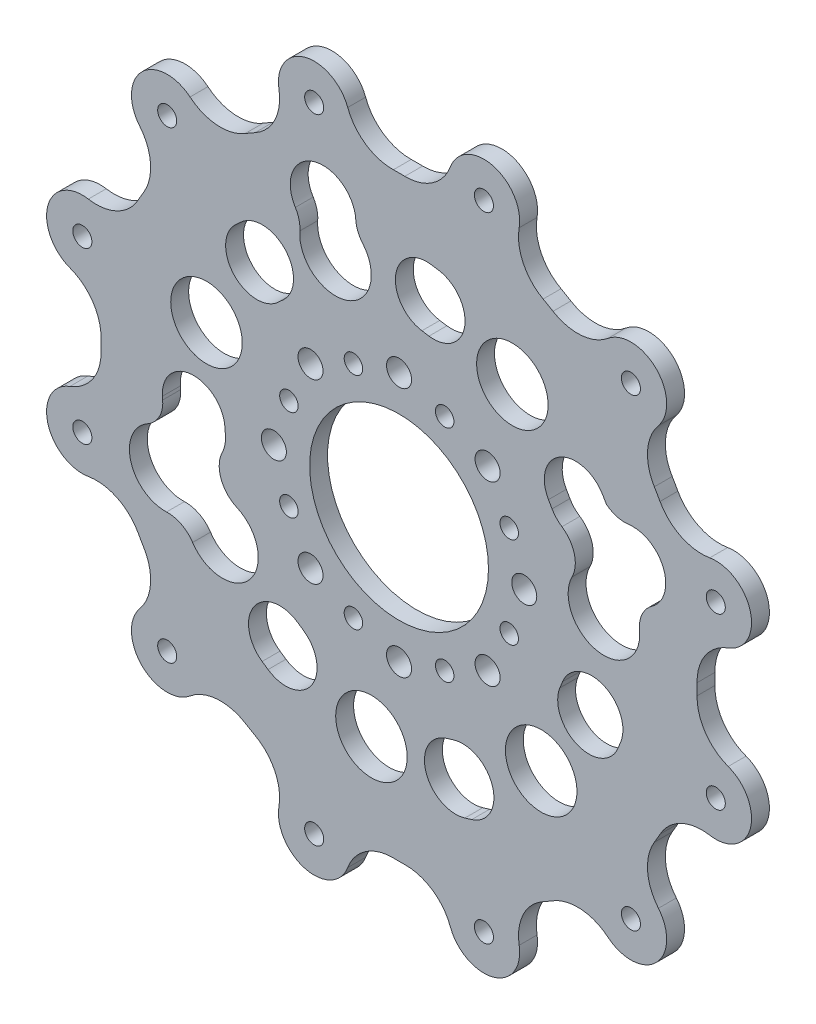
SolidWorks part; units mm, degrees
ref_plane "Front Plane" through (0, 0, 0) normal (0, 0, 1) x (1, 0, 0)
ref_plane "Top Plane" through (0, 0, 0) normal (0, 1, 0) x (1, 0, 0)
ref_plane "Right Plane" through (0, 0, 0) normal (1, 0, 0) x (0, 0, -1)
sketch "Sketch1" plane through (0, 0, 0) normal (0, 0, 1) x (1, 0, 0)
  line L0 (-65, 0) -> (-65, -65) construction
  line L2 (65, -65) -> (65, 0) construction
  line L7 (-65, -65) -> (65, -65) construction
  circle A0 centre (0, 0) radius 15
  arc A1 (65, 0) -> (-65, 0) centre (0, 0) ccw
  arc A2 (-65, 0) -> (0, -65) centre (0, 0) ccw
  arc A3 (0, -65) -> (65, 0) centre (0, 0) ccw
  dimension "D1" = 130
  dimension "D2" = 30
extrude "Boss-Extrude1" add sketch "Sketch1" along normal blind 3
sketch "Sketch2" plane through (0, 0, 3) normal (0, 0, 1) x (1, 0, 0)
  line L0 (0, 0) -> (0, 61) construction
  circle A0 centre (0, 61) radius 2.5
  circle A1 centre (52.8275, 30.5) radius 2.5
  circle A2 centre (52.8275, -30.5) radius 2.5
  circle A3 centre (0, -61) radius 2.5
  circle A4 centre (-52.8275, -30.5) radius 2.5
  circle A5 centre (-52.8275, 30.5) radius 2.5
  point P16 (0, 0)
  dimension "D1" = 5
  dimension "D2" = 61
  dimension "D3" = 6
extrude "Cut-Extrude1" cut sketch "Sketch2" against normal through all
sketch "Sketch3" plane through (0, 0, 3) normal (0, 0, 1) x (1, 0, 0)
  line L0 (0, 0) -> (14.235, 53.1259) construction
  line L1 (0, 0) -> (0, 26.2737) construction
  circle A0 centre (14.235, 53.1259) radius 1.6
  circle A1 centre (38.8909, 38.8909) radius 1.6
  circle A2 centre (53.1259, 14.235) radius 1.6
  circle A3 centre (53.1259, -14.235) radius 1.6
  circle A4 centre (38.8909, -38.8909) radius 1.6
  circle A5 centre (14.235, -53.1259) radius 1.6
  circle A6 centre (-14.235, -53.1259) radius 1.6
  circle A7 centre (-38.8909, -38.8909) radius 1.6
  circle A8 centre (-53.1259, -14.235) radius 1.6
  circle A9 centre (-53.1259, 14.235) radius 1.6
  circle A10 centre (-38.8909, 38.8909) radius 1.6
  circle A11 centre (-14.235, 53.1259) radius 1.6
  point P29 (0, 0)
  dimension "D1" = 3.2
  dimension "D2" = 55
  dimension "D3" = 15
  dimension "D4" = 12
extrude "Cut-Extrude2" cut sketch "Sketch3" against normal through all
sketch "Sketch4" plane through (0, 0, 3) normal (0, 0, 1) x (1, 0, 0)
  line L0 (0, 21) -> (0, 0) construction
  line L1 (0, 0) -> (7.6537, 18.4776) construction
  circle A0 centre (0, 21) radius 2.1
  circle A1 centre (7.6537, 18.4776) radius 1.55
  circle A2 centre (14.8492, 14.8492) radius 2.1
  circle A3 centre (18.4776, 7.6537) radius 1.55
  circle A4 centre (21, 0) radius 2.1
  circle A5 centre (18.4776, -7.6537) radius 1.55
  circle A6 centre (14.8492, -14.8492) radius 2.1
  circle A7 centre (7.6537, -18.4776) radius 1.55
  circle A8 centre (0, -21) radius 2.1
  circle A9 centre (-7.6537, -18.4776) radius 1.55
  circle A10 centre (-14.8492, -14.8492) radius 2.1
  circle A11 centre (-18.4776, -7.6537) radius 1.55
  circle A12 centre (-21, 0) radius 2.1
  circle A13 centre (-18.4776, 7.6537) radius 1.55
  circle A14 centre (-14.8492, 14.8492) radius 2.1
  circle A15 centre (-7.6537, 18.4776) radius 1.55
  point P37 (0, 0)
  dimension "D2" = 4.2
  dimension "D3" = 3.1
  dimension "D1" = 22.5
  dimension "D4" = 21
  dimension "D5" = 20
  dimension "D6" = 8
extrude "Cut-Extrude3" cut sketch "Sketch4" against normal through all
sketch "Sketch5" plane through (0, 0, 3) normal (0, 0, 1) x (1, 0, 0)
  line L0 (28.9526, 32.8899) -> (20.9782, 23.831)
  line L1 (18.0715, 39.9177) -> (13.094, 28.9231)
  line L2 (-26.3114, 9.5766) -> (0, 0) construction
  line L3 (33.6015, 28.1237) -> (24.3466, 20.3775)
  line L4 (40.3558, 17.0707) -> (29.2406, 12.3689)
  line L5 (42.4763, 10.7594) -> (30.777, 7.7959)
  line L6 (43.766, -2.1296) -> (31.7115, -1.543)
  line L7 (42.9381, -8.7359) -> (31.1116, -6.3297)
  line L8 (38.5078, -20.908) -> (27.9016, -15.1493)
  line L9 (34.8956, -26.5009) -> (25.2843, -19.2017)
  line L10 (25.6227, -35.5454) -> (18.5654, -25.7551)
  line L11 (19.9415, -39.0171) -> (14.449, -28.2706)
  line L12 (7.6627, -43.1426) -> (5.5521, -31.2598)
  line L13 (0, 0) -> (-15.7436, 0) construction
  line L14 (1.0378, -43.8055) -> (0.752, -31.7401)
  line L15 (-11.815, -42.1948) -> (-8.5608, -30.5731)
  line L16 (-18.0715, -39.9177) -> (-13.094, -28.9231)
  line L17 (-28.9526, -32.8899) -> (-20.9782, -23.831)
  line L18 (-33.6015, -28.1237) -> (-24.3466, -20.3775)
  line L19 (-40.3558, -17.0707) -> (-29.2406, -12.3689)
  line L20 (-42.4763, -10.7594) -> (-30.777, -7.7959)
  line L21 (-43.766, 2.1296) -> (-31.7115, 1.543)
  line L22 (-42.9381, 8.7359) -> (-31.1116, 6.3297)
  line L23 (-38.5078, 20.908) -> (-27.9016, 15.1493)
  line L24 (-34.8956, 26.5009) -> (-25.2843, 19.2017)
  line L25 (-25.6227, 35.5454) -> (-18.5654, 25.7551)
  line L26 (-19.9415, 39.0171) -> (-14.449, 28.2706)
  line L27 (-7.6627, 43.1426) -> (-5.5521, 31.2598)
  line L28 (-1.0378, 43.8055) -> (-0.752, 31.7401)
  line L29 (11.815, 42.1948) -> (8.5608, 30.5731)
  arc A0 (14.6457, 23.8642) -> (15.7288, 23.1647) centre (0, 0) cw
  arc A1 (23.6896, 41.7469) -> (28.3093, 38.7632) centre (0, 0) cw
  arc A2 (14.6457, 23.8642) -> (13.094, 28.9231) centre (16.738, 27.2734) cw
  arc A3 (15.7288, 23.1647) -> (20.9782, 23.831) centre (17.9758, 26.474) ccw
  arc A4 (28.3093, 38.7632) -> (28.9526, 32.8899) centre (25.9502, 35.5329) cw
  arc A5 (23.6896, 41.7469) -> (18.0715, 39.9177) centre (21.7154, 38.268) ccw
  arc A6 (39.4569, 27.3341) -> (33.6015, 28.1237) centre (36.1688, 25.0563) ccw
  arc A7 (23.5497, 15.1464) -> (24.3466, 20.3775) centre (26.9139, 17.3102) cw
  arc A8 (23.5497, 15.1464) -> (24.222, 14.0462) centre (0, 0) cw
  arc A9 (24.222, 14.0462) -> (29.2406, 12.3689) centre (27.6822, 16.0529) ccw
  arc A10 (42.3245, 22.6414) -> (40.3558, 17.0707) centre (38.7975, 20.7546) cw
  arc A11 (39.4569, 27.3341) -> (42.3245, 22.6414) centre (0, 0) cw
  arc A12 (47.4093, 7.5075) -> (42.4763, 10.7594) centre (43.4585, 6.8819) ccw
  arc A13 (27.7893, 3.4286) -> (30.777, 7.7959) centre (31.7592, 3.9184) cw
  arc A14 (27.7893, 3.4286) -> (27.9177, 2.1457) centre (0, 0) cw
  arc A15 (27.9177, 2.1457) -> (31.7115, -1.543) centre (31.9059, 2.4522) ccw
  arc A16 (47.9568, 2.0353) -> (43.766, -2.1296) centre (43.9604, 1.8657) cw
  arc A17 (47.4093, 7.5075) -> (47.9568, 2.0353) centre (0, 0) cw
  arc A18 (45.9716, -13.8061) -> (42.9381, -8.7359) centre (42.1407, -12.6556) ccw
  arc A19 (26.5249, -8.9683) -> (31.1116, -6.3297) centre (30.3142, -10.2494) cw
  arc A20 (26.5249, -8.9683) -> (26.0839, -10.1798) centre (0, 0) cw
  arc A21 (26.0839, -10.1798) -> (27.9016, -15.1493) centre (29.8102, -11.6341) ccw
  arc A22 (44.0907, -18.9739) -> (38.5078, -20.908) centre (40.4165, -17.3928) cw
  arc A23 (45.9716, -13.8061) -> (44.0907, -18.9739) centre (0, 0) cw
  arc A24 (35.4288, -32.3852) -> (34.8956, -26.5009) centre (32.4764, -29.6864) ccw
  arc A25 (20.0069, -19.5888) -> (25.2843, -19.2017) centre (22.8651, -22.3872) cw
  arc A26 (20.0069, -19.5888) -> (19.084, -20.4891) centre (0, 0) cw
  arc A27 (19.084, -20.4891) -> (18.5654, -25.7551) centre (21.8102, -23.4161) ccw
  arc A28 (31.4919, -36.2252) -> (25.6227, -35.5454) centre (28.8675, -33.2064) cw
  arc A29 (35.4288, -32.3852) -> (31.4919, -36.2252) centre (0, 0) cw
  arc A30 (17.8688, -44.55) -> (19.9415, -39.0171) centre (16.3798, -40.8375) ccw
  arc A31 (9.5263, -26.3296) -> (14.449, -28.2706) centre (10.8872, -30.091) cw
  arc A32 (9.5263, -26.3296) -> (8.3042, -26.7402) centre (0, 0) cw
  arc A33 (8.3042, -26.7402) -> (5.5521, -31.2598) centre (9.4905, -30.5603) ccw
  arc A34 (12.6557, -46.3016) -> (7.6627, -43.1426) centre (11.601, -42.4431) cw
  arc A35 (17.8688, -44.55) -> (12.6557, -46.3016) centre (0, 0) cw
  arc A36 (-3.2303, -47.8912) -> (1.0378, -43.8055) centre (-2.9611, -43.9003) ccw
  arc A37 (-2.8411, -27.8555) -> (0.752, -31.7401) centre (-3.2469, -31.8348) cw
  arc A38 (-2.8411, -27.8555) -> (-4.1203, -27.6952) centre (0, 0) cw
  arc A39 (-4.1203, -27.6952) -> (-8.5608, -30.5731) centre (-4.709, -31.6516) ccw
  arc A40 (-8.6871, -47.2073) -> (-11.815, -42.1948) centre (-7.9632, -43.2734) cw
  arc A41 (-3.2303, -47.8912) -> (-8.6871, -47.2073) centre (0, 0) cw
  arc A42 (-23.6896, -41.7469) -> (-18.0715, -39.9177) centre (-21.7154, -38.268) ccw
  arc A43 (-14.6457, -23.8642) -> (-13.094, -28.9231) centre (-16.738, -27.2734) cw
  arc A44 (-14.6457, -23.8642) -> (-15.7288, -23.1647) centre (0, 0) cw
  arc A45 (-15.7288, -23.1647) -> (-20.9782, -23.831) centre (-17.9758, -26.474) ccw
  arc A46 (-28.3093, -38.7632) -> (-28.9526, -32.8899) centre (-25.9502, -35.5329) cw
  arc A47 (-23.6896, -41.7469) -> (-28.3093, -38.7632) centre (0, 0) cw
  arc A48 (-39.4569, -27.3341) -> (-33.6015, -28.1237) centre (-36.1688, -25.0563) ccw
  arc A49 (-23.5497, -15.1464) -> (-24.3466, -20.3775) centre (-26.9139, -17.3102) cw
  arc A50 (-23.5497, -15.1464) -> (-24.222, -14.0462) centre (0, 0) cw
  arc A51 (-24.222, -14.0462) -> (-29.2406, -12.3689) centre (-27.6822, -16.0529) ccw
  arc A52 (-42.3245, -22.6414) -> (-40.3558, -17.0707) centre (-38.7975, -20.7546) cw
  arc A53 (-39.4569, -27.3341) -> (-42.3245, -22.6414) centre (0, 0) cw
  arc A54 (-47.4093, -7.5075) -> (-42.4763, -10.7594) centre (-43.4585, -6.8819) ccw
  arc A55 (-27.7893, -3.4286) -> (-30.777, -7.7959) centre (-31.7592, -3.9184) cw
  arc A56 (-27.7893, -3.4286) -> (-27.9177, -2.1457) centre (0, 0) cw
  arc A57 (-27.9177, -2.1457) -> (-31.7115, 1.543) centre (-31.9059, -2.4522) ccw
  arc A58 (-47.9568, -2.0353) -> (-43.766, 2.1296) centre (-43.9604, -1.8657) cw
  arc A59 (-47.4093, -7.5075) -> (-47.9568, -2.0353) centre (0, 0) cw
  arc A60 (-45.9716, 13.8061) -> (-42.9381, 8.7359) centre (-42.1407, 12.6556) ccw
  arc A61 (-26.5249, 8.9683) -> (-31.1116, 6.3297) centre (-30.3142, 10.2494) cw
  arc A62 (-26.5249, 8.9683) -> (-26.0839, 10.1798) centre (0, 0) cw
  arc A63 (-26.0839, 10.1798) -> (-27.9016, 15.1493) centre (-29.8102, 11.6341) ccw
  arc A64 (-44.0907, 18.9739) -> (-38.5078, 20.908) centre (-40.4165, 17.3928) cw
  arc A65 (-45.9716, 13.8061) -> (-44.0907, 18.9739) centre (0, 0) cw
  arc A66 (-35.4288, 32.3852) -> (-34.8956, 26.5009) centre (-32.4764, 29.6864) ccw
  arc A67 (-20.0069, 19.5888) -> (-25.2843, 19.2017) centre (-22.8651, 22.3872) cw
  arc A68 (-20.0069, 19.5888) -> (-19.084, 20.4891) centre (0, 0) cw
  arc A69 (-19.084, 20.4891) -> (-18.5654, 25.7551) centre (-21.8102, 23.4161) ccw
  arc A70 (-31.4919, 36.2252) -> (-25.6227, 35.5454) centre (-28.8675, 33.2064) cw
  arc A71 (-35.4288, 32.3852) -> (-31.4919, 36.2252) centre (0, 0) cw
  arc A72 (-17.8688, 44.55) -> (-19.9415, 39.0171) centre (-16.3798, 40.8375) ccw
  arc A73 (-9.5263, 26.3296) -> (-14.449, 28.2706) centre (-10.8872, 30.091) cw
  arc A74 (-9.5263, 26.3296) -> (-8.3042, 26.7402) centre (0, 0) cw
  arc A75 (-8.3042, 26.7402) -> (-5.5521, 31.2598) centre (-9.4905, 30.5603) ccw
  arc A76 (-12.6557, 46.3016) -> (-7.6627, 43.1426) centre (-11.601, 42.4431) cw
  arc A77 (-17.8688, 44.55) -> (-12.6557, 46.3016) centre (0, 0) cw
  arc A78 (3.2303, 47.8912) -> (-1.0378, 43.8055) centre (2.9611, 43.9003) ccw
  arc A79 (2.8411, 27.8555) -> (-0.752, 31.7401) centre (3.2469, 31.8348) cw
  arc A80 (2.8411, 27.8555) -> (4.1203, 27.6952) centre (0, 0) cw
  arc A81 (4.1203, 27.6952) -> (8.5608, 30.5731) centre (4.709, 31.6516) ccw
  arc A82 (8.6871, 47.2073) -> (11.815, 42.1948) centre (7.9632, 43.2734) cw
  arc A83 (3.2303, 47.8912) -> (8.6871, 47.2073) centre (0, 0) cw
  point P77 (0, 0)
  dimension "D2" = 28
  dimension "D3" = 48
  dimension "D4" = 4
  dimension "D1" = 20
  dimension "D6" = 17
  dimension "D5" = 14
extrude "Cut-Extrude4" [suppressed] cut sketch "Sketch5" against normal through all
sketch "Sketch6" [suppressed] plane through (0, 0, 0) normal (0, 0, -1) x (-1, 0, 0)
  line L0 (29.2406, -12.3689) -> (40.3558, -17.0707) construction
  line L1 (42.4763, -10.7594) -> (30.777, -7.7959) construction
  line L2 (29.2406, -12.3689) -> (40.3558, -17.0707)
  line L3 (42.4763, -10.7594) -> (30.777, -7.7959)
  line L4 (-42.4763, 10.7594) -> (-30.777, 7.7959) construction
  line L5 (-29.2406, 12.3689) -> (-40.3558, 17.0707) construction
  line L6 (-42.4763, 10.7594) -> (-30.777, 7.7959)
  line L7 (-29.2406, 12.3689) -> (-40.3558, 17.0707)
  arc A0 (-27.7893, 3.4286) -> (-30.777, 7.7959) centre (-31.7592, 3.9184) ccw construction
  arc A1 (-29.2406, 12.3689) -> (-24.222, 14.0462) centre (-27.6822, 16.0529) ccw construction
  arc A2 (-42.4763, 10.7594) -> (-47.4093, 7.5075) centre (-43.4585, 6.8819) ccw construction
  arc A3 (-42.3245, 22.6414) -> (-40.3558, 17.0707) centre (-38.7975, 20.7546) ccw construction
  arc A4 (-27.7893, 3.4286) -> (-30.777, 7.7959) centre (-31.7592, 3.9184) ccw
  arc A5 (-29.2406, 12.3689) -> (-24.222, 14.0462) centre (-27.6822, 16.0529) ccw
  arc A6 (-42.4763, 10.7594) -> (-47.4093, 7.5075) centre (-43.4585, 6.8819) ccw
  arc A7 (-42.3245, 22.6414) -> (-40.3558, 17.0707) centre (-38.7975, 20.7546) ccw
  arc A8 (29.2406, -12.3689) -> (24.222, -14.0462) centre (27.6822, -16.0529) ccw construction
  arc A9 (27.7893, -3.4286) -> (30.777, -7.7959) centre (31.7592, -3.9184) ccw construction
  arc A10 (42.3245, -22.6414) -> (40.3558, -17.0707) centre (38.7975, -20.7546) ccw construction
  arc A11 (42.4763, -10.7594) -> (47.4093, -7.5075) centre (43.4585, -6.8819) ccw construction
  arc A12 (29.2406, -12.3689) -> (24.222, -14.0462) centre (27.6822, -16.0529) ccw
  arc A13 (27.7893, -3.4286) -> (30.777, -7.7959) centre (31.7592, -3.9184) ccw
  arc A14 (42.3245, -22.6414) -> (40.3558, -17.0707) centre (38.7975, -20.7546) ccw
  arc A15 (42.4763, -10.7594) -> (47.4093, -7.5075) centre (43.4585, -6.8819) ccw
  arc A16 (-42.3245, 22.6414) -> (-47.4093, 7.5075) centre (0, 0) ccw
  arc A17 (-24.222, 14.0462) -> (-27.7893, 3.4286) centre (0, 0) ccw
  arc A18 (24.222, -14.0462) -> (27.7893, -3.4286) centre (0, 0) ccw
  arc A19 (42.3245, -22.6414) -> (47.4093, -7.5075) centre (0, 0) ccw
extrude "Cut-Extrude5" [suppressed] cut sketch "Sketch6" against normal through all
sketch "Sketch7" plane through (0, 0, 0) normal (0, 0, -1) x (-1, 0, 0)
  line L1 (29.2118, -1.5122) -> (29.1248, -2.7133)
  line L2 (30.2092, -1.5845) -> (30.1222, -2.7855)
  line L3 (38.6, -3.3996) -> (38.687, -2.1985)
  line L4 (30.2092, -1.5845) -> (30.1222, -2.7855) construction
  line L5 (38.6, -3.3996) -> (38.687, -2.1985) construction
  line L6 (20.0739, 22.6306) -> (20.9587, 21.8138)
  line L7 (26.7246, 28.0591) -> (25.8398, 28.876)
  line L24 (20.0739, 22.6306) -> (20.9587, 21.8138) construction
  line L25 (26.7246, 28.0591) -> (25.8398, 28.876) construction
  line L26 (-5.1775, 29.8044) -> (-3.9871, 29.9868)
  line L27 (-5.275, 38.3887) -> (-6.4653, 38.2063)
  line L28 (-5.1775, 29.8044) -> (-3.9871, 29.9868) construction
  line L29 (-5.275, 38.3887) -> (-6.4653, 38.2063) construction
  line L30 (-26.5301, 14.5348) -> (-25.9306, 15.5792)
  line L31 (-33.3024, 19.8108) -> (-33.9019, 18.7665)
  line L32 (-26.5301, 14.5348) -> (-25.9306, 15.5792) construction
  line L33 (-33.3024, 19.8108) -> (-33.9019, 18.7665) construction
  line L34 (-27.905, -11.6797) -> (-28.3478, -10.5599)
  line L35 (-36.2524, -13.685) -> (-35.8097, -14.8049)
  line L36 (-27.905, -11.6797) -> (-28.3478, -10.5599) construction
  line L37 (-36.2524, -13.685) -> (-35.8097, -14.8049) construction
  line L38 (-8.2669, -29.0992) -> (-9.4185, -28.7472)
  line L39 (-11.9037, -36.8757) -> (-10.7521, -37.2278)
  line L40 (-8.2669, -29.0992) -> (-9.4185, -28.7472) construction
  line L41 (-11.9037, -36.8757) -> (-10.7521, -37.2278) construction
  line L42 (17.5964, -24.6064) -> (16.6031, -25.2872)
  line L43 (21.4088, -32.2983) -> (22.4021, -31.6175)
  line L44 (17.5964, -24.6064) -> (16.6031, -25.2872) construction
  line L45 (21.4088, -32.2983) -> (22.4021, -31.6175) construction
  line L46 (39.5974, -3.4718) -> (39.6844, -2.2708)
  line L47 (19.3956, 21.8959) -> (20.2804, 21.079)
  line L48 (27.403, 28.7938) -> (26.5182, 29.6107)
  line L49 (-5.0259, 28.8159) -> (-3.8356, 28.9984)
  line L50 (-5.4265, 39.3772) -> (-6.6168, 39.1947)
  line L51 (-25.6628, 14.037) -> (-25.0633, 15.0814)
  line L52 (-34.1696, 20.3087) -> (-34.7692, 19.2643)
  line L53 (-26.9751, -11.3121) -> (-27.4178, -10.1922)
  line L54 (-37.1824, -14.0527) -> (-36.7396, -15.1725)
  line L55 (-7.9745, -28.1429) -> (-9.1261, -27.7908)
  line L56 (-12.196, -37.832) -> (-11.0444, -38.1841)
  line L57 (17.031, -23.7816) -> (16.0377, -24.4624)
  line L58 (21.9742, -33.1231) -> (22.9675, -32.4423)
  arc A0 (29.1248, -2.7133) -> (35.2378, -8.2688) centre (34.3611, -3.0926) ccw
  circle A1 centre (39.2311, -12.747) radius 5
  circle A2 centre (39.2311, -12.747) radius 5 construction
  circle A3 centre (-39.2311, 12.747) radius 5
  circle A4 centre (-39.2311, 12.747) radius 5 construction
  arc A5 (39.6844, -2.2708) -> (29.2118, -1.5122) centre (34.4481, -1.8915) ccw
  circle A7 centre (-19.0059, 28.7928) radius 5
  circle A24 centre (-19.0059, 28.7928) radius 5 construction
  circle A25 centre (-34.3611, 3.0926) radius 5
  arc A26 (8.3928, 37.2673) -> (15.1153, 35.0831) centre (10.6611, 32.8114) ccw
  arc A27 (8.3928, 37.2673) -> (8.5374, 37.6407) centre (8.2567, 37.5347) ccw
  arc A28 (15.2178, 35.4701) -> (8.5374, 37.6407) centre (12.747, 39.2311) ccw
  arc A29 (15.2178, 35.4701) -> (15.1153, 35.0831) centre (15.3825, 35.2194) ccw
  arc A30 (8.3928, 37.2673) -> (15.1153, 35.0831) centre (10.6611, 32.8114) ccw construction
  arc A31 (8.3928, 37.2673) -> (8.5374, 37.6407) centre (8.2567, 37.5347) ccw construction
  arc A32 (15.2178, 35.4701) -> (8.5374, 37.6407) centre (12.747, 39.2311) ccw construction
  arc A33 (15.2178, 35.4701) -> (15.1153, 35.0831) centre (15.3825, 35.2194) ccw construction
  circle A34 centre (-34.3611, 3.0926) radius 5 construction
  circle A35 centre (-23.8417, -24.9364) radius 5
  circle A36 centre (-23.8417, -24.9364) radius 5 construction
  circle A37 centre (4.631, -34.1878) radius 5
  circle A38 centre (4.631, -34.1878) radius 5 construction
  circle A39 centre (29.6165, -17.695) radius 5
  circle A40 centre (29.6165, -17.695) radius 5 construction
  circle A41 centre (32.3001, 12.1224) radius 5
  circle A42 centre (32.3001, 12.1224) radius 5 construction
  arc A43 (20.2804, 21.079) -> (27.403, 28.7938) centre (23.8417, 24.9364) ccw
  arc A44 (38.687, -2.1985) -> (30.2092, -1.5845) centre (34.4481, -1.8915) ccw
  arc A45 (30.1222, -2.7855) -> (38.6, -3.3996) centre (34.3611, -3.0926) ccw
  arc A46 (38.687, -2.1985) -> (30.2092, -1.5845) centre (34.4481, -1.8915) ccw construction
  arc A47 (30.1222, -2.7855) -> (38.6, -3.3996) centre (34.3611, -3.0926) ccw construction
  arc A48 (25.8398, 28.876) -> (20.0739, 22.6306) centre (22.9569, 25.7533) ccw
  arc A49 (20.9587, 21.8138) -> (26.7246, 28.0591) centre (23.8417, 24.9364) ccw
  arc A50 (25.8398, 28.876) -> (20.0739, 22.6306) centre (22.9569, 25.7533) ccw construction
  arc A51 (20.9587, 21.8138) -> (26.7246, 28.0591) centre (23.8417, 24.9364) ccw construction
  arc A52 (-6.4653, 38.2063) -> (-5.1775, 29.8044) centre (-5.8214, 34.0053) ccw
  arc A53 (-3.9871, 29.9868) -> (-5.275, 38.3887) centre (-4.631, 34.1878) ccw
  arc A54 (-6.4653, 38.2063) -> (-5.1775, 29.8044) centre (-5.8214, 34.0053) ccw construction
  arc A55 (-3.9871, 29.9868) -> (-5.275, 38.3887) centre (-4.631, 34.1878) ccw construction
  arc A56 (-33.9019, 18.7665) -> (-26.5301, 14.5348) centre (-30.216, 16.6506) ccw
  arc A57 (-25.9306, 15.5792) -> (-33.3024, 19.8108) centre (-29.6165, 17.695) ccw
  arc A58 (-33.9019, 18.7665) -> (-26.5301, 14.5348) centre (-30.216, 16.6506) ccw construction
  arc A59 (-25.9306, 15.5792) -> (-33.3024, 19.8108) centre (-29.6165, 17.695) ccw construction
  arc A60 (-35.8097, -14.8049) -> (-27.905, -11.6797) centre (-31.8574, -13.2423) ccw
  arc A61 (-28.3478, -10.5599) -> (-36.2524, -13.685) centre (-32.3001, -12.1224) ccw
  arc A62 (-35.8097, -14.8049) -> (-27.905, -11.6797) centre (-31.8574, -13.2423) ccw construction
  arc A63 (-28.3478, -10.5599) -> (-36.2524, -13.685) centre (-32.3001, -12.1224) ccw construction
  arc A64 (-10.7521, -37.2278) -> (-8.2669, -29.0992) centre (-9.5095, -33.1635) ccw
  arc A65 (-9.4185, -28.7472) -> (-11.9037, -36.8757) centre (-10.6611, -32.8114) ccw
  arc A66 (-10.7521, -37.2278) -> (-8.2669, -29.0992) centre (-9.5095, -33.1635) ccw construction
  arc A67 (-9.4185, -28.7472) -> (-11.9037, -36.8757) centre (-10.6611, -32.8114) ccw construction
  arc A68 (22.4021, -31.6175) -> (17.5964, -24.6064) centre (19.9992, -28.1119) ccw
  arc A69 (16.6031, -25.2872) -> (21.4088, -32.2983) centre (19.0059, -28.7928) ccw
  arc A70 (22.4021, -31.6175) -> (17.5964, -24.6064) centre (19.9992, -28.1119) ccw construction
  arc A71 (16.6031, -25.2872) -> (21.4088, -32.2983) centre (19.0059, -28.7928) ccw construction
  arc A72 (26.5182, 29.6107) -> (19.3956, 21.8959) centre (22.9569, 25.7533) ccw
  arc A73 (-3.8356, 28.9984) -> (-5.4265, 39.3772) centre (-4.631, 34.1878) ccw
  arc A74 (-6.6168, 39.1947) -> (-5.0259, 28.8159) centre (-5.8214, 34.0053) ccw
  arc A75 (-25.0633, 15.0814) -> (-34.1696, 20.3087) centre (-29.6165, 17.695) ccw
  arc A76 (-34.7692, 19.2643) -> (-35.4649, 16.7552) centre (-30.216, 16.6506) ccw
  arc A77 (-27.4178, -10.1922) -> (-37.1824, -14.0527) centre (-32.3001, -12.1224) ccw
  arc A78 (-36.7396, -15.1725) -> (-26.9751, -11.3121) centre (-31.8574, -13.2423) ccw
  arc A79 (-9.1261, -27.7908) -> (-12.196, -37.832) centre (-10.6611, -32.8114) ccw
  arc A80 (-11.0444, -38.1841) -> (-7.9745, -28.1429) centre (-9.5095, -33.1635) ccw
  arc A81 (16.0377, -24.4624) -> (21.9742, -33.1231) centre (19.0059, -28.7928) ccw
  arc A82 (22.9675, -32.4423) -> (17.031, -23.7816) centre (19.9992, -28.1119) ccw
  arc A83 (35.2378, -8.2688) -> (33.2332, -12.9076) centre (39.2311, -12.747) ccw
  circle A85 centre (-19.0059, 28.7928) radius 6
  arc A86 (7.4203, 37.861) -> (16.2509, 34.9917) centre (10.6611, 32.8114) ccw
  arc A87 (16.2509, 34.9917) -> (16.2509, 34.9917) centre (16.2509, 34.9917) ccw
  arc A88 (16.2509, 34.9917) -> (7.4203, 37.861) centre (12.747, 39.2311) ccw
  arc A89 (7.4203, 37.861) -> (7.4203, 37.861) centre (7.4203, 37.861) ccw
  arc A90 (-38.6616, 7.2765) -> (-35.17, 9.0378) centre (-34.3611, 3.0926) ccw
  circle A91 centre (-23.8417, -24.9364) radius 6
  circle A92 centre (4.631, -34.1878) radius 6
  arc A93 (33.2332, -12.9076) -> (35.6143, -17.5343) centre (29.6165, -17.695) ccw
  circle A94 centre (32.3001, 12.1224) radius 6
  circle A95 centre (39.2311, -12.747) radius 6 construction
  arc A96 (38.003, -6.874) -> (39.5974, -3.4718) centre (34.3611, -3.0926) ccw
  arc A97 (29.1248, -2.7133) -> (39.5974, -3.4718) centre (34.3611, -3.0926) ccw construction
  arc A98 (35.6143, -17.5343) -> (38.003, -6.874) centre (39.2311, -12.747) ccw
  circle A99 centre (29.6165, -17.695) radius 6 construction
  arc A100 (-35.17, 9.0378) -> (-33.7311, 12.7511) centre (-39.2311, 12.747) ccw
  arc A101 (-33.7311, 12.7511) -> (-25.6628, 14.037) centre (-30.216, 16.6506) ccw
  arc A102 (-34.7692, 19.2643) -> (-25.6628, 14.037) centre (-30.216, 16.6506) ccw construction
  arc A103 (-35.4649, 16.7552) -> (-38.6616, 7.2765) centre (-39.2311, 12.747) ccw
  circle A104 centre (-34.3611, 3.0926) radius 6 construction
  dimension "D1" = 0
  dimension "D2" = 0
  dimension "D3" = 1
  dimension "D4" = 0
  dimension "D5" = 0
  dimension "D6" = 0
  dimension "D7" = 0
  dimension "D8" = 0
  dimension "D9" = 0
  dimension "D10" = 0
  dimension "D11" = 0
  dimension "D12" = 0
  dimension "D13" = 0
  dimension "D14" = 0
  dimension "D15" = 0
  dimension "D16" = 0
  dimension "D17" = 0
extrude "Cut-Extrude8" cut sketch "Sketch7" against normal through all
fillet "Fillet1" radius 5 6 edges at (38.6616, 7.2765, 1.5) (35.4649, 16.7552, 1.5) (-16.2509, 34.9917, 1.5) (-7.4203, 37.861, 1.5) (-35.6143, -17.5343, 1.5) (-38.003, -6.874, 1.5)
sketch "Sketch8" plane through (0, 0, 3) normal (0, 0, 1) x (1, 0, 0)
  arc A0 (-29.6543, -5.4182) -> (-27.192, -12.2067) centre (-25.1716, -7.633) ccw
  arc A1 (-35.2378, -8.2688) -> (-29.1248, -2.7133) centre (-34.3611, -3.0926) ccw construction
  arc A2 (-34.6297, -20.9916) -> (-33.2332, -12.9076) centre (-29.6165, -17.695) ccw construction
  arc A3 (-33.2332, -12.9076) -> (-35.2378, -8.2688) centre (-39.2311, -12.747) ccw construction
  arc A4 (-27.192, -12.2067) -> (-33.2332, -12.9076) centre (-29.6165, -17.695) ccw
  arc A5 (-33.2332, -12.9076) -> (-35.2378, -8.2688) centre (-39.2311, -12.747) ccw
  arc A6 (-35.2378, -8.2688) -> (-29.6543, -5.4182) centre (-34.3611, -3.0926) ccw
  arc A7 (35.17, 9.0378) -> (40.3315, 3.6876) centre (34.3611, 3.0926) ccw construction
  arc A8 (33.7311, 12.7511) -> (35.17, 9.0378) centre (39.2311, 12.747) ccw construction
  arc A9 (25.6628, 14.037) -> (33.7311, 12.7511) centre (30.216, 16.6506) ccw construction
  arc A10 (35.17, 9.0378) -> (29.0184, 5.823) centre (34.3611, 3.0926) ccw
  arc A11 (33.7311, 12.7511) -> (35.17, 9.0378) centre (39.2311, 12.747) ccw
  arc A12 (27.3222, 12.2702) -> (33.7311, 12.7511) centre (30.216, 16.6506) ccw
  arc A13 (27.3222, 12.2702) -> (29.0184, 5.823) centre (24.5661, 8.0984) cw
  dimension "D1" = 5
extrude "Cut-Extrude9" cut sketch "Sketch8" against normal through all
sketch "Sketch9" plane through (0, 0, 3) normal (0, 0, 1) x (1, 0, 0)
  circle A0 centre (-14.235, 53.1259) radius 6
  circle A1 centre (0, 0) radius 50
  arc A3 (-20.1498, 52.1179) -> (-24.169, 43.7705) centre (-28.036, 50.7738) cw
  arc A4 (-8.6087, 55.2103) -> (-0.9543, 49.9909) centre (-1.107, 57.9894) ccw
  circle A5 centre (0, 0) radius 65 construction
  circle A6 centre (0, 0) radius 65
  circle A7 centre (14.235, 53.1259) radius 6
  arc A8 (8.6087, 55.2103) -> (0.9543, 49.9909) centre (1.107, 57.9894) cw
  arc A9 (20.1498, 52.1179) -> (24.169, 43.7705) centre (28.036, 50.7738) ccw
  circle A10 centre (38.8909, 38.8909) radius 6
  arc A11 (35.0605, 43.5091) -> (25.8219, 42.8162) centre (29.9534, 49.6668) cw
  arc A12 (43.5091, 35.0605) -> (42.8162, 25.8219) centre (49.6668, 29.9534) ccw
  circle A13 centre (53.1259, 14.235) radius 6
  arc A14 (52.1179, 20.1498) -> (43.7705, 24.169) centre (50.7738, 28.036) cw
  arc A15 (55.2103, 8.6087) -> (49.9909, 0.9543) centre (57.9894, 1.107) ccw
  circle A16 centre (53.1259, -14.235) radius 6
  arc A17 (55.2103, -8.6087) -> (49.9909, -0.9543) centre (57.9894, -1.107) cw
  arc A18 (52.1179, -20.1498) -> (43.7705, -24.169) centre (50.7738, -28.036) ccw
  circle A19 centre (38.8909, -38.8909) radius 6
  arc A20 (43.5091, -35.0605) -> (42.8162, -25.8219) centre (49.6668, -29.9534) cw
  arc A21 (35.0605, -43.5091) -> (25.8219, -42.8162) centre (29.9534, -49.6668) ccw
  circle A22 centre (14.235, -53.1259) radius 6
  arc A23 (20.1498, -52.1179) -> (24.169, -43.7705) centre (28.036, -50.7738) cw
  arc A24 (8.6087, -55.2103) -> (0.9543, -49.9909) centre (1.107, -57.9894) ccw
  circle A25 centre (-14.235, -53.1259) radius 6
  arc A26 (-8.6087, -55.2103) -> (-0.9543, -49.9909) centre (-1.107, -57.9894) cw
  arc A27 (-20.1498, -52.1179) -> (-24.169, -43.7705) centre (-28.036, -50.7738) ccw
  circle A28 centre (-38.8909, -38.8909) radius 6
  arc A29 (-35.0605, -43.5091) -> (-25.8219, -42.8162) centre (-29.9534, -49.6668) cw
  arc A30 (-43.5091, -35.0605) -> (-42.8162, -25.8219) centre (-49.6668, -29.9534) ccw
  circle A31 centre (-53.1259, -14.235) radius 6
  arc A32 (-52.1179, -20.1498) -> (-43.7705, -24.169) centre (-50.7738, -28.036) cw
  arc A33 (-55.2103, -8.6087) -> (-49.9909, -0.9543) centre (-57.9894, -1.107) ccw
  circle A34 centre (-53.1259, 14.235) radius 6
  arc A35 (-55.2103, 8.6087) -> (-49.9909, 0.9543) centre (-57.9894, 1.107) cw
  arc A36 (-52.1179, 20.1498) -> (-43.7705, 24.169) centre (-50.7738, 28.036) ccw
  circle A37 centre (-38.8909, 38.8909) radius 6
  arc A38 (-43.5091, 35.0605) -> (-42.8162, 25.8219) centre (-49.6668, 29.9534) cw
  arc A39 (-35.0605, 43.5091) -> (-25.8219, 42.8162) centre (-29.9534, 49.6668) ccw
  point P105 (0, 0)
  dimension "D1" = 100
  dimension "D2" = 12
  dimension "D3" = 8
  dimension "D4" = 12
extrude "Cut-Extrude10" cut sketch "Sketch9" against normal through all contours A6 A37 A39 A1 A3 A0 A4 A8 A7 A9 A11 A10 A12 A14 A13 A15 A17 A16 A18 A20 A19 A21 A23 A22 A24 A26 A25 A27 A29 A28 A30 A32 A31 A33 A35 A34 A36 A38
